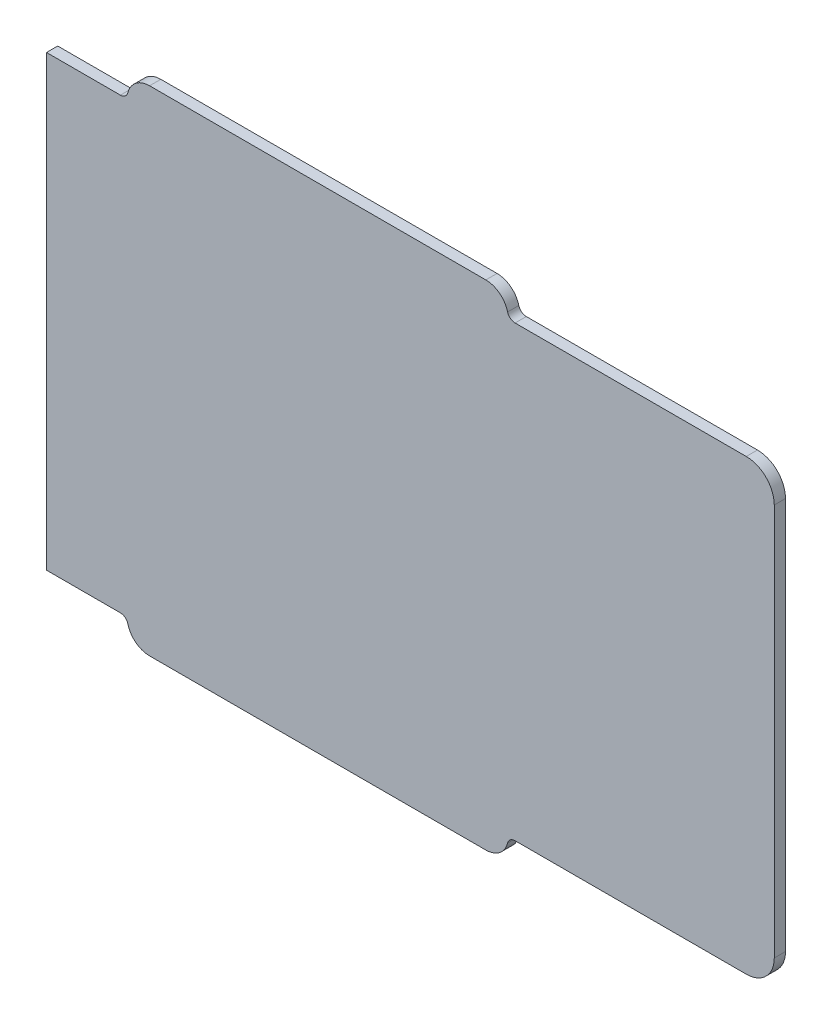
SolidWorks part; units mm, degrees
ref_plane "Front Plane" through (0, 0, 0) normal (0, 0, 1) x (1, 0, 0)
ref_plane "Top Plane" through (0, 0, 0) normal (0, 1, 0) x (1, 0, 0)
ref_plane "Right Plane" through (0, 0, 0) normal (1, 0, 0) x (0, 0, -1)
sketch "Sketch1" plane through (0, 0, 0) normal (0, 0, 1) x (1, 0, 0)
  line L0 (120.3, 160) -> (146.6617, 160)
  line L1 (10, 160) -> (146.6617, 160) construction
  line L2 (157.08, 168.1) -> (277.08, 168.1) construction
  line L3 (157.08, 168.1) -> (277.08, 168.1)
  line L4 (287.4983, 160) -> (370, 160)
  line L5 (380, 150) -> (380, 10)
  line L6 (287.4983, 0) -> (370, 0) construction
  line L7 (370, 0) -> (287.4983, 0)
  line L8 (277.08, -8.1) -> (157.08, -8.1)
  line L9 (10, 0) -> (146.6617, 0) construction
  line L10 (120.3, 160) -> (120.3, 0)
  line L11 (120.3, 0) -> (146.6617, 0)
  line L12 (120, 0) -> (120, 160) construction
  arc A0 (146.6617, 160) -> (149.3269, 162.0721) centre (146.6617, 162.75) ccw
  arc A1 (157.08, 168.1) -> (149.3269, 162.0721) centre (157.08, 160.1) ccw construction
  arc A2 (149.3269, 162.0721) -> (157.08, 168.1) centre (157.08, 160.1) cw
  arc A3 (277.08, 168.1) -> (284.8331, 162.0721) centre (277.08, 160.1) cw
  arc A4 (284.8331, 162.0721) -> (287.4983, 160) centre (287.4983, 162.75) ccw construction
  arc A5 (284.8331, 162.0721) -> (287.4983, 160) centre (287.4983, 162.75) ccw
  arc A6 (370, 160) -> (380, 150) centre (370, 150) cw
  arc A7 (380, 150) -> (370, 160) centre (370, 150) ccw construction
  arc A8 (380, 10) -> (370, 0) centre (370, 10) cw
  arc A9 (287.4983, 0) -> (284.8331, -2.0721) centre (287.4983, -2.75) ccw
  arc A10 (277.08, -8.1) -> (284.8331, -2.0721) centre (277.08, -0.1) ccw construction
  arc A11 (284.8331, -2.0721) -> (277.08, -8.1) centre (277.08, -0.1) cw
  arc A12 (157.08, -8.1) -> (149.3269, -2.0721) centre (157.08, -0.1) cw
  arc A13 (149.3269, -2.0721) -> (157.08, -8.1) centre (157.08, -0.1) ccw construction
  arc A14 (149.3269, -2.0721) -> (146.6617, 0) centre (146.6617, -2.75) ccw
  point P66 (0, 0)
  dimension "D1" = 0.3
extrude "Boss-Extrude1" add sketch "Sketch1" along normal blind 4 contours L3 A3 A5 L4 A6 L5 A8 L7 A9 A11 L8 A12 A14 L11 L10 L0 A0 A2
sketch "Sketch2" plane through (0, 0, 0) normal (0, 0, -1) x (-1, 0, 0)
  circle A0 centre (-126.25, 8.75) radius 2.75
  circle A1 centre (-126.25, 151.25) radius 2.75
  circle A2 centre (-370, 10) radius 2.75
  circle A3 centre (-370, 150) radius 2.75
extrude "Cut-Extrude1" cut sketch "Sketch2" against normal blind 3
sketch "Sketch3" plane through (0, 0, 0) normal (0, 0, -1) x (-1, 0, 0)
  circle A0 centre (-157.08, -0.1) radius 2.35
  circle A1 centre (-157.08, -0.1) radius 2.75 construction
  circle A2 centre (-157.08, 160.1) radius 2.35
  circle A3 centre (-277.08, 160.1) radius 2.35
  circle A4 centre (-277.08, -0.1) radius 2.35
  circle A5 centre (-277.08, -0.1) radius 2.75 construction
  circle A6 centre (-277.08, 160.1) radius 2.75 construction
  circle A7 centre (-157.08, 160.1) radius 2.75 construction
  dimension "D1" = 0.4
  dimension "D2" = 0.4
  dimension "D3" = 0.4
  dimension "D4" = 0.4
extrude "Boss-Extrude2" add sketch "Sketch3" along normal blind 4
chamfer "Chamfer1" distance 1 angle 45 4 edges at (154.73, -0.1, -4) (274.73, -0.1, -4) (274.73, 160.1, -4) (154.73, 160.1, -4)
sketch "Sketch4" plane through (0, 0, 0) normal (0, 0, -1) x (-1, 0, 0)
  line L0 (-364.25, 10) -> (-364.25, 3)
  line L1 (-281.003, 3) -> (-364.3091, 3) construction
  line L2 (-364.25, 3) -> (-272.08, 3)
  line L3 (-272.08, 3) -> (-272.08, -5.1)
  line L4 (-272.08, -5.1) -> (-162.08, -5.1)
  line L5 (-162.08, -5.1) -> (-162.08, 3)
  line L6 (-162.08, 3) -> (-132, 3)
  line L7 (-132, 3) -> (-132, 8.75)
  line L8 (-126.25, 14.5) -> (-122.8675, 14.5)
  line L9 (-126.25, 14.5) -> (-111.25, 14.5) construction
  line L10 (-122.8675, 14.5) -> (-122.8675, 145.5)
  line L11 (-126.25, 145.5) -> (-111.25, 145.5) construction
  line L12 (-122.8675, 145.5) -> (-126.25, 145.5)
  line L13 (-132, 151.25) -> (-132, 157)
  line L14 (-132, 157) -> (-162.08, 157)
  line L15 (-162.08, 157) -> (-162.08, 165.1)
  line L16 (-162.08, 165.1) -> (-272.08, 165.1)
  line L17 (-272.08, 165.1) -> (-272.08, 157)
  line L18 (-272.08, 157) -> (-364.25, 157)
  line L19 (-281.003, 157) -> (-364.3091, 157) construction
  line L20 (-364.25, 157) -> (-364.25, 150)
  line L21 (-370, 144.25) -> (-377, 144.25)
  line L22 (-377, 15.6909) -> (-377, 144.3091) construction
  line L23 (-377, 144.25) -> (-377, 15.75)
  line L24 (-377, 15.75) -> (-370, 15.75)
  arc A0 (-132, 8.75) -> (-126.25, 14.5) centre (-126.25, 8.75) cw
  arc A1 (-126.25, 14.5) -> (-132, 8.75) centre (-126.25, 8.75) ccw construction
  arc A2 (-126.25, 145.5) -> (-132, 151.25) centre (-126.25, 151.25) cw
  arc A3 (-132, 151.25) -> (-126.25, 145.5) centre (-126.25, 151.25) ccw construction
  arc A4 (-364.25, 150) -> (-370, 144.25) centre (-370, 150) cw
  arc A5 (-370, 144.25) -> (-364.25, 150) centre (-370, 150) ccw construction
  arc A6 (-370, 15.75) -> (-364.25, 10) centre (-370, 10) cw
  arc A7 (-364.25, 10) -> (-370, 15.75) centre (-370, 10) ccw construction
extrude "Cut-Extrude2" cut sketch "Sketch4" against normal blind 2.5 contours L24 A6 L0 L2 L3 L4 L5 L6 L7 A0 L8 L10 L12 A2 L13 L14 L15 L16 L17 L18 L20 A4 L21 L23 region at (248.1495, 80, 0)
